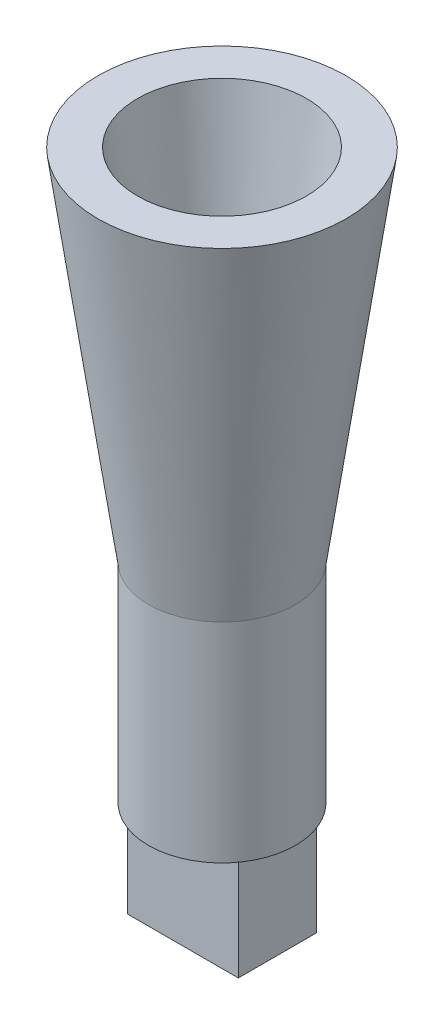
SolidWorks part; units mm, degrees
ref_plane "Front Plane" through (0, 0, 0) normal (0, 0, 1) x (1, 0, 0)
ref_plane "Top Plane" through (0, 0, 0) normal (0, 1, 0) x (1, 0, 0)
ref_plane "Right Plane" through (0, 0, 0) normal (1, 0, 0) x (0, 0, -1)
sketch "Sketch1" plane through (0, 0, 0) normal (0, 1, 0) x (1, 0, 0)
  line L1 (-54, 38.1) -> (54, 38.1)
  line L2 (-54, 38.1) -> (-54, -38.1)
  line L3 (-54, -38.1) -> (54, -38.1)
  line L4 (54, 38.1) -> (54, -38.1)
  line L5 (-54, 38.1) -> (54, -38.1) construction
  line L6 (-54, -38.1) -> (54, 38.1) construction
  point P0 (0, 0)
  dimension "D1" = 108
  dimension "D2" = 76.2
extrude "Boss-Extrude1" add sketch "Sketch1" along normal blind 101.6
sketch "Sketch2" plane through (0, 101.6, 0) normal (0, 1, 0) x (1, 0, 0)
  circle A0 centre (0, 0) radius 71.6161
extrude "Boss-Extrude2" add sketch "Sketch2" along normal blind 203.2
sketch "Sketch4" plane through (0, 304.8, 0) normal (0, 1, 0) x (1, 0, 0)
  circle A0 centre (0, 0) radius 71.6161
extrude "Boss-Extrude3" add sketch "Sketch4" along normal blind 350 draft 8 draft outward yes
shell "Shell1" thickness 38.1 removed face at (0, 654.8, 120.8054)
